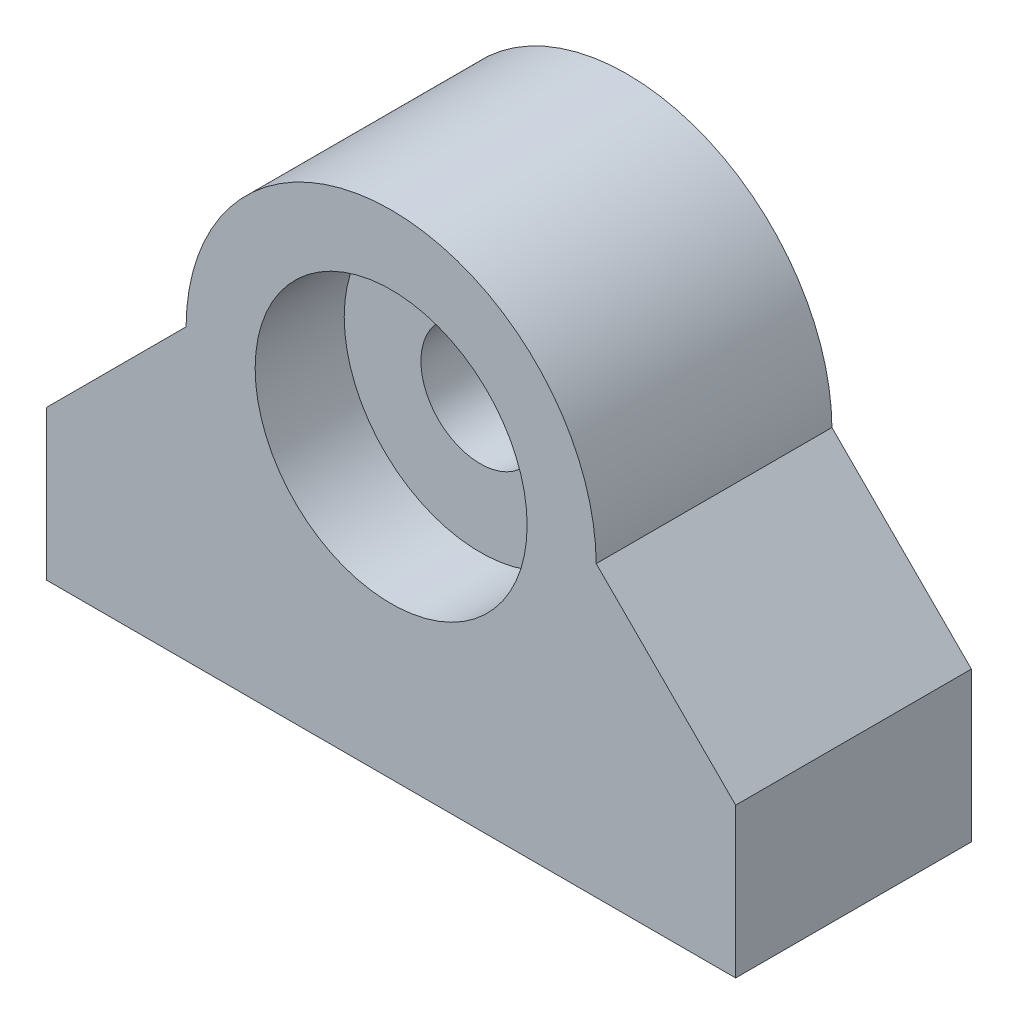
SolidWorks part; units mm, degrees
ref_plane "Front Plane" through (0, 0, 0) normal (0, 0, 1) x (1, 0, 0)
ref_plane "Top Plane" through (0, 0, 0) normal (0, 1, 0) x (1, 0, 0)
ref_plane "Right Plane" through (0, 0, 0) normal (1, 0, 0) x (0, 0, -1)
sketch "Sketch1" plane through (0, 0, 0) normal (0, 0, 1) x (1, 0, 0)
  line L0 (0, -26.1041) -> (0, 52.7781) construction
  line L3 (0, 0) -> (-19, 0)
  line L4 (19, 0) -> (19, 8.255)
  line L5 (19, 8.255) -> (11.3098, 15.9452)
  line L7 (-19, 0) -> (-19, 8.255)
  line L8 (0, 0) -> (19, 0)
  line L9 (-19, 8.255) -> (-11.3098, 15.9452)
  circle A0 centre (0, 15.874) radius 7.5
  arc A1 (-11.3098, 15.9452) -> (11.3098, 15.9452) centre (0, 15.874) cw
  point P3 (0, 0)
  point P11 (0, 4.699)
  point P12 (0, 28.448)
  point P15 (0, 8.374)
  dimension "D6" = 15
  dimension "D3" = 3.81
  dimension "D1" = 8.255
  dimension "D4" = 45
  dimension "D5" = 15.874
  dimension "D7" = 38
extrude "Boss-Extrude1" add sketch "Sketch1" along normal blind 13
ref_plane "Plane1" through (0, 0, 6.5) normal (0, 0, 1) x (1, 0, 0)
sketch "Sketch3" plane through (0, 0, 6.5) normal (0, 0, 1) x (1, 0, 0)
  circle A0 centre (0, 15.874) radius 3.2703
  circle A1 centre (0, 15.874) radius 8.7376
  dimension "D1" = 6.5405
  dimension "D2" = 17.4752
extrude "Boss-Extrude2" add sketch "Sketch3" along normal blind 1.5875 and the other way blind 1.5875
sketch "Sketch7" plane through (0, 0, 0) normal (0, -1, 0) x (1, 0, 0)
  line L0 (-19, 13) -> (19, 0) construction
  line L1 (0, 0) -> (0, 13) construction
  line L2 (-19, 13) -> (19, 13) construction
  point P9 (0, 6.5)
hole_wizard "M4x0.7 Tapped Hole1" positions "Sketch5" profile "Sketch6" tap size "M4x0.7" standard "ANSI Metric"
sketch "Sketch5" plane through (0, 0, 0) normal (0, -1, 0) x (-1, 0, 0)
  point P0 (10, -6.5)
  point P2 (-10, -6.5)
  dimension "D1" = 10
  dimension "D2" = 0
  dimension "D3" = 10
  dimension "D4" = 0
sketch "Sketch6" plane through (-10, 0, 6.5) normal (1, 0, 0) x (0, 0, -1)
  line L0 (0, 0) -> (0, 11.1006)
  line L1 (0, 11.1006) -> (1.65, 10.1092)
  line L2 (1.65, 10.1092) -> (1.65, 0)
  line L5 (1.65, 0) -> (0, 0)
  line L10 (0, 11.1006) -> (-1.65, 10.1092) construction
  line L11 (0, -6.35) -> (0, 107.95) construction
  dimension "Tap Drill Dia." = 3.3
  dimension "Tap Drill Depth" = 10.1092
  dimension "Drill Angle" = 118
cosmetic thread "Hole Thread1" parameters "D1"=8.001, "D2"=4
cosmetic thread "Hole Thread2" parameters "D1"=8.001, "D2"=4
equation "\"0.095inin\"=0.085"
